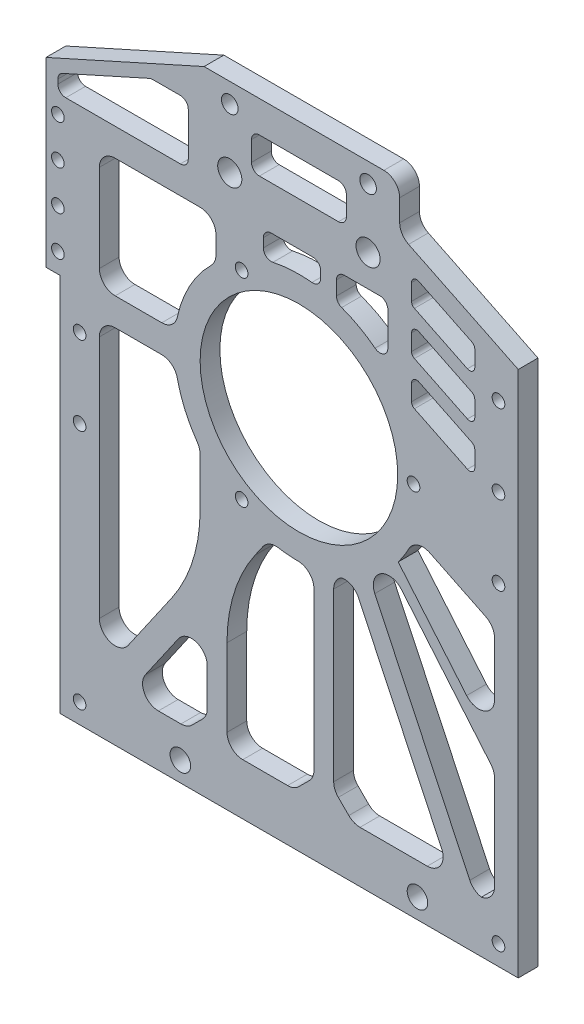
SolidWorks part; units mm, degrees
material "环氧树脂FR-4"
ref_plane "前视基准面" through (0, 0, 0) normal (0, 0, 1) x (1, 0, 0)
ref_plane "上视基准面" through (0, 0, 0) normal (0, 1, 0) x (1, 0, 0)
ref_plane "右视基准面" through (0, 0, 0) normal (1, 0, 0) x (0, 0, -1)
sketch "草图1" plane through (0, 0, 0) normal (0, 0, 1) x (1, 0, 0)
  line L1 (55.5, -80) -> (-55.5, -80)
  line L2 (55.5, -80) -> (55.5, 80)
  line L3 (55.5, 80) -> (-55.5, 80)
  line L4 (-55.5, -80) -> (-55.5, 80)
  line L5 (55.5, -80) -> (-55.5, 80) construction
  line L6 (55.5, 80) -> (-55.5, -80) construction
  point P0 (0, 0)
  dimension "D1" = 111
  dimension "D2" = 160
extrude "凸台-拉伸1" add sketch "草图1" along normal blind 5
sketch "草图2" plane through (0, 0, 5) normal (0, 0, 1) x (1, 0, 0)
  line L0 (0, 80) -> (0, -80) construction
  line L1 (55.5, 80) -> (-55.5, 80) construction
  line L2 (-55.5, -80) -> (55.5, -80) construction
  circle A0 centre (-30, -75) radius 2.6
  circle A1 centre (30, -75) radius 2.6
  dimension "D3" = 5.2
  dimension "D1" = 60
  dimension "D2" = 5
extrude "切除-拉伸1" cut sketch "草图2" against normal through all
sketch "草图3" plane through (0, 0, 5) normal (0, 0, 1) x (1, 0, 0)
  line L0 (0, 0) -> (0, 15) construction
  line L1 (-55.5, -80) -> (55.5, -80) construction
  circle A0 centre (0, 15) radius 25
  dimension "D1" = 50
  dimension "D2" = 95
extrude "切除-拉伸2" cut sketch "草图3" against normal through all
sketch "草图4" plane through (0, 0, 5) normal (0, 0, 1) x (1, 0, 0)
  line L0 (0, 15) -> (-14.5, 40.1147) construction
  line L1 (0, 15) -> (0, 40) construction
  circle A0 centre (-14.5, 40.1147) radius 1.6
  circle A1 centre (29, 15) radius 1.6
  circle A2 centre (-14.5, -10.1147) radius 1.6
  circle A3 centre (0, 15) radius 25 construction
  point P2 (0, 15)
  dimension "D3" = 3.2
  dimension "D2" = 29
  dimension "D4" = 30
  dimension "D1" = 3
extrude "切除-拉伸3" cut sketch "草图4" against normal through all
sketch "草图5" plane through (0, 0, 5) normal (0, 0, 1) x (1, 0, 0)
  point P0 (0, 15)
sketch "草图6" plane through (0, 0, 5) normal (0, 0, 1) x (1, 0, 0)
  line L0 (0, 80) -> (0, -80) construction
  line L1 (55.5, 80) -> (-55.5, 80) construction
  line L2 (-55.5, -80) -> (55.5, -80) construction
  line L4 (17.5, 60) -> (-17.5, 60) construction
  line L5 (17.5, 60) -> (17.5, 75) construction
  line L6 (17.5, 75) -> (-17.5, 75) construction
  line L7 (-17.5, 60) -> (-17.5, 75) construction
  line L8 (17.5, 60) -> (-17.5, 75) construction
  line L9 (17.5, 75) -> (-17.5, 60) construction
  circle A2 centre (-17.5, 75) radius 2.1
  circle A3 centre (17.5, 75) radius 2.1
  circle A4 centre (17.5, 60) radius 3.0525
  circle A5 centre (-17.5, 60) radius 3.0525
  point P6 (0, 67.5)
  dimension "D4" = 4.2
  dimension "D5" = 6.105
  dimension "D1" = 35
  dimension "D2" = 15
  dimension "D3" = 12.5
extrude "切除-拉伸4" cut sketch "草图6" against normal through all
sketch "草图7" plane through (0, 0, 5) normal (0, 0, 1) x (1, 0, 0)
  line L0 (-17.5, 75) -> (-17.5, 60) construction
  line L2 (17.5, 75) -> (17.5, 60) construction
  line L4 (-17.5, 67.5) -> (17.5, 67.5) construction
  line L6 (10, 63) -> (-10, 63)
  line L7 (12, 65) -> (12, 70)
  line L8 (10, 72) -> (-10, 72)
  line L9 (-12, 65) -> (-12, 70)
  line L10 (12, 63) -> (-12, 72) construction
  line L11 (12, 72) -> (-12, 63) construction
  arc A0 (12, 70) -> (10, 72) centre (10, 70) ccw
  arc A1 (10, 63) -> (12, 65) centre (10, 65) ccw
  arc A2 (-10, 63) -> (-12, 65) centre (-10, 65) cw
  arc A3 (-10, 72) -> (-12, 70) centre (-10, 70) ccw
  point P10 (0, 67.5)
  dimension "D3" = 2
  dimension "D1" = 24
  dimension "D2" = 9
extrude "切除-拉伸5" cut sketch "草图7" against normal through all
sketch "草图8" plane through (0, 0, 5) normal (0, 0, 1) x (1, 0, 0)
  line L5 (25.5, 80) -> (25.5, 68)
  line L8 (55.5, 80) -> (-55.5, 80) construction
  line L9 (25.5, 68) -> (55.5, 53.368)
  line L10 (55.5, -80) -> (55.5, 80) construction
  line L11 (55.5, 53.368) -> (55.5, 80)
  line L12 (55.5, 80) -> (25.5, 80)
  dimension "D1" = 26
  dimension "D2" = 12
  dimension "D3" = 30
extrude "切除-拉伸6" cut sketch "草图8" against normal through all
fillet "圆角1" radius 4 2 edges at (25.5, 80, 2.5) (25.5, 68, 2.5)
sketch "草图10" plane through (0, 0, 0) normal (0, 0, 1) x (1, 0, 0)
  line L0 (-55.5, 80) -> (-64, 80)
  line L1 (-64, 80) -> (-64, 16)
  line L2 (-64, 16) -> (-55.5, 16)
  line L3 (-55.5, 80) -> (-55.5, -80) construction
  line L4 (-55.5, 16) -> (-55.5, 80)
  dimension "D1" = 8.5
  dimension "D2" = 64
extrude "凸台-拉伸3" add sketch "草图10" along normal up to surface (5 mm away) up to face at (12.5699, 33.4098, 5)
sketch "草图11" plane through (0, 0, 5) normal (0, 0, 1) x (1, 0, 0)
  line L0 (-61, 41) -> (-61, 21) construction
  line L1 (-64, 80) -> (-64, 16) construction
  line L2 (-64, 16) -> (-55.5, 16) construction
  line L3 (-61, 51) -> (-61, 41) construction
  circle A0 centre (-61, 21) radius 1.6
  circle A1 centre (-61, 41) radius 1.6
  circle A2 centre (-61, 31) radius 1.6
  circle A3 centre (-61, 51) radius 1.6
  dimension "D3" = 3.2
  dimension "D1" = 20
  dimension "D2" = 3
  dimension "D4" = 5
  dimension "D5" = 10
extrude "切除-拉伸7" cut sketch "草图11" against normal through all
sketch "草图12" plane through (0, 0, 5) normal (0, 0, 1) x (1, 0, 0)
  line L0 (-64, 80) -> (-64, 62)
  line L1 (-64, 80) -> (-64, 16) construction
  line L2 (-64, 62) -> (-24, 80)
  line L3 (21.5, 80) -> (-64, 80) construction
  line L4 (-24, 80) -> (-64, 80)
  dimension "D1" = 18
  dimension "D2" = 40
extrude "切除-拉伸8" cut sketch "草图12" against normal through all
sketch "草图13" plane through (0, 0, 0) normal (0, 0, 1) x (1, 0, 0)
  line L0 (-55.5, -80) -> (-60.5, -80)
  line L1 (-60.5, -80) -> (-60.5, 16)
  line L2 (-64, 16) -> (-55.5, 16) construction
  line L3 (-60.5, 16) -> (-55.5, 16)
  line L4 (-55.5, 16) -> (-55.5, -80) construction
  line L5 (-55.5, 16) -> (-55.5, -80)
  dimension "D1" = 5
extrude "凸台-拉伸4" add sketch "草图13" along normal up to surface (5 mm away) up to face at (-4.6764, 32.8435, 5)
sketch "草图19" plane through (0, 0, 5) normal (0, 0, 1) x (1, 0, 0)
  line L0 (-55.5, -75) -> (50.5, -75) construction
  line L1 (-60.5, 16) -> (-60.5, -80) construction
  line L2 (-60.5, -80) -> (55.5, -80) construction
  line L3 (-55.5, 6) -> (-55.5, -14) construction
  line L4 (-64, 16) -> (-60.5, 16) construction
  line L5 (50.5, 44) -> (50.5, 24) construction
  line L6 (55.5, -80) -> (55.5, 53.368) construction
  line L7 (50.5, 24) -> (50.5, 4) construction
  circle A0 centre (-55.5, -75) radius 1.6
  circle A1 centre (50.5, -75) radius 1.6
  circle A2 centre (-55.5, 6) radius 1.6
  circle A3 centre (-55.5, -14) radius 1.6
  circle A4 centre (50.5, 44) radius 1.6
  circle A5 centre (50.5, 24) radius 1.6
  circle A6 centre (50.5, 4) radius 1.6
  dimension "D1" = 3.2
  dimension "D2" = 5
  dimension "D11" = 20
  dimension "D3" = 5
  dimension "D4" = 20
  dimension "D5" = 5
  dimension "D6" = 10
  dimension "D7" = 5
  dimension "D8" = 20
  dimension "D9" = 5
  dimension "D10" = 44
extrude "切除-拉伸13" cut sketch "草图19" against normal through all
sketch "草图14" plane through (0, 0, 5) normal (0, 0, 1) x (1, 0, 0)
  line L0 (28.5, 60.9738) -> (44.5, 53.1701)
  line L1 (44.5, 53.1701) -> (44.5, 46.1701)
  line L2 (44.5, 46.1701) -> (28.5, 53.9738)
  line L3 (28.5, 53.9738) -> (28.5, 60.9738)
  line L4 (27.7465, 66.9043) -> (55.5, 53.368) construction
  line L5 (55.5, -80) -> (55.5, 53.368) construction
  line L6 (25.5, 76) -> (25.5, 70.4995) construction
  dimension "D1" = 5
  dimension "D2" = 11
  dimension "D3" = 3
  dimension "D4" = 7
extrude "切除-拉伸9" cut sketch "草图14" against normal through all
fillet "圆角2" radius 1.3 4 edges at (44.5, 46.1701, 2.5) (44.5, 53.1701, 2.5) (28.5, 53.9738, 2.5) (28.5, 60.9738, 2.5)
pattern_linear "阵列(线性)1" count 3 spacing 11 along (0, -1, 0) of "切除-拉伸9", "圆角2"
sketch "草图17" plane through (0, 0, 5) normal (0, 0, 1) x (1, 0, 0)
  line L0 (-61, 60.0602) -> (-37.4444, 70.6602)
  line L1 (-28, 70.6602) -> (-28, 55.6602)
  line L3 (-64, 62) -> (-24, 80) construction
  line L4 (-61, 60.0602) -> (-61, 55.6602)
  line L5 (-61, 55.6602) -> (-28, 55.6602)
  line L6 (-64, 62) -> (-64, 16) construction
  line L7 (-37.4444, 70.6602) -> (-28, 70.6602)
  dimension "D1" = 3
  dimension "D2" = 3
  dimension "D3" = 4.4
  dimension "D4" = 33
  dimension "D5" = 15
extrude "切除-拉伸11" cut sketch "草图17" against normal through all
sketch "草图16" plane through (0, 0, 5) normal (0, 0, 1) x (1, 0, 0)
  line L0 (-27, 70.9739) -> (-53, 59.2739)
  line L1 (-53, 59.2739) -> (-53, 48.2739)
  line L2 (-53, 48.2739) -> (-27, 59.9739)
  line L3 (-27, 59.9739) -> (-27, 70.9739)
  line L5 (-22.8002, 51.1888) -> (-22.8002, 20.9929)
  line L8 (-64, 62) -> (-24, 80) construction
  line L13 (-64, 62) -> (-64, 16) construction
  line L21 (-51.6219, 38.219) -> (-51.6219, 20.984)
  line L22 (-51.6219, 38.219) -> (-22.8002, 51.1888)
  line L23 (-22.8002, 20.9929) -> (-51.6219, 20.984)
  circle A0 centre (0, 15) radius 29
  circle A1 centre (0, 15) radius 34
  dimension "D1" = 68
  dimension "D2" = 7
  dimension "D3" = 11
  dimension "D4" = 11
  dimension "D5" = 3
  dimension "D6" = 6
fillet "圆角3" radius 2 5 edges at (-61, 60.0602, 2.5) (-28, 55.6602, 2.5) (-28, 70.6602, 2.5) (-37.4444, 70.6602, 2.5) (-61, 55.6602, 2.5)
sketch "草图18" plane through (0, 0, 5) normal (0, 0, 1) x (1, 0, 0)
  line L0 (-50.5, 48.6602) -> (-21, 48.6602)
  line L1 (-21, 48.6602) -> (-21, 38.4787)
  line L2 (-50.5, 48.6602) -> (-50.5, 18.5)
  line L3 (-50.5, 18.5) -> (-31.305, 18.5)
  line L4 (-60.5, 16) -> (-60.5, -80) construction
  line L5 (8.7974, -15.2466) -> (8.7974, -67)
  line L6 (8.7974, -67) -> (38.7974, -67)
  line L7 (-31.305, 11.5) -> (-50.5, 11.5)
  line L8 (-50.5, 11.5) -> (-50.5, -67)
  line L9 (-50.5, -67) -> (-25, -30.1638)
  line L10 (-25, -30.1638) -> (-25, -4.1638)
  line L11 (-43.2026, -67) -> (-23.2026, -38.1088)
  line L12 (-43.2026, -67) -> (-23.2026, -67)
  line L13 (3.7974, -67) -> (3.7974, -16.2703)
  line L14 (38.7974, -67) -> (13.472, -13.4737)
  line L15 (29.4362, 3.7858) -> (49.5, -6)
  line L16 (49.5, -6) -> (49.5, -67)
  line L17 (44.3288, -67) -> (17.8209, -10.9743)
  line L18 (-23.2026, -38.1088) -> (-23.2026, -67)
  line L19 (-18.2026, -30.886) -> (-18.2026, -67)
  line L20 (-18.2026, -67) -> (3.7974, -67)
  line L21 (-18.2026, -30.886) -> (-7.5997, -15.5695)
  line L22 (-59, 55.6602) -> (-30, 55.6602) construction
  line L23 (-60.5, -80) -> (55.5, -80) construction
  line L24 (44.3288, -67) -> (49.5, -67)
  line L25 (55.5, -80) -> (55.5, 53.368) construction
  line L26 (27.7465, 66.9043) -> (55.5, 53.368) construction
  line L27 (25.1247, -4) -> (49.5, -33.0494)
  line L28 (49.5, -37.7165) -> (23.1711, -6.339)
  circle A0 centre (0, 15) radius 31.5
  circle A1 centre (50.5, 4) radius 1.6 construction
  dimension "D1" = 63
  dimension "D2" = 10
  dimension "D3" = 3.5
  dimension "D4" = 7
  dimension "D5" = 21
  dimension "D6" = 3.5
  dimension "D7" = 25
  dimension "D8" = 13
  dimension "D9" = 6
  dimension "D10" = 13
  dimension "D11" = 20
  dimension "D12" = 5
  dimension "D13" = 26
  dimension "D14" = 22
  dimension "D15" = 5
  dimension "D16" = 13
  dimension "D17" = 30
  dimension "D18" = 5
  dimension "D19" = 6
  dimension "D20" = 10
  dimension "D21" = 40
  dimension "D22" = 3
  dimension "D23" = 19
extrude "切除-拉伸12" cut sketch "草图18" against normal blind 10 contours A0 L1 L0 L2 L3 | A0 L7 L8 L9 L10 | A0 L11 L12 L13 | A0 L5 L6 L14 | A0 L21 L19 L20 L13 | A0 L17 L24 L16 L28 | A0 L27 L16 L15 | L11 L18 L12 region at (-37.6585, 34.9225, 5) region at (-39.5472, -20.5511, 5) region at (39.8826, -11.5595, 5) region at (-6.6688, -43.084, 5) region at (36.9414, -36.5854, 5) region at (19.0491, -46.9108, 5) region at (-29.8693, -57.3696, 5)
fillet "圆角5" radius 40 2 edges at (-25, -30.1638, 2.5) (-18.2026, -30.886, 2.5)
chamfer "倒角1" distance 5 angle 45 3 edges at (-23.2026, -67, 2.5) (8.7974, -67, 2.5) (3.7974, -67, 2.5)
fillet "圆角6" radius 4 31 edges at (-31.305, 18.5, 2.5) (-50.5, 18.5, 2.5) (-50.5, 48.6602, 2.5) (-21, 48.6602, 2.5) (-21, 38.4787, 2.5) (38.7974, -67, 2.5) (13.7974, -67, 2.5) (8.7974, -62, 2.5) (8.7974, -15.2466, 2.5) (-25, -4.1638, 2.5) (-50.5, -67, 2.5) (-50.5, 11.5, 2.5) (-31.305, 11.5, 2.5) (-23.2026, -38.1088, 2.5) (-23.2026, -62, 2.5) (-28.2026, -67, 2.5) (-43.2026, -67, 2.5) (49.5, -67, 2.5) (44.3288, -67, 2.5) (17.8209, -10.9743, 2.5) (3.7974, -62, 2.5) (-1.2026, -67, 2.5) (-18.2026, -67, 2.5) (49.5, -6, 2.5) (29.4362, 3.7858, 2.5) (13.472, -13.4737, 2.5) (3.7974, -16.2703, 2.5) (-7.5997, -15.5695, 2.5) (49.5, -37.7165, 2.5) (49.5, -33.0494, 2.5) (23.1711, -6.339, 2.5)
sketch "草图20" plane through (0, 0, 5) normal (0, 0, 1) x (1, 0, 0)
  line L0 (-9, 45.1869) -> (-9, 52)
  line L1 (-9, 52) -> (22.5, 52)
  line L2 (22.5, 52) -> (22.5, 37.0454)
  line L3 (-21, 44.6602) -> (-21, 40.2042) construction
  line L4 (28.5, 47.8934) -> (28.5, 43.7861) construction
  line L5 (5.5, 52) -> (5.5, 46.0161)
  line L6 (9.5, 52) -> (9.5, 45.0333)
  arc A0 (22.5, 37.0454) -> (-9, 45.1869) centre (0, 15) ccw
  circle A1 centre (17.5, 60) radius 3.0525 construction
  dimension "D1" = 63
  dimension "D2" = 12
  dimension "D3" = 8
  dimension "D4" = 6
  dimension "D5" = 13
  dimension "4" = 4
extrude "切除-拉伸14" cut sketch "草图20" against normal through all contours A0 L5 L1 L0 | A0 L2 L1 L6 region at (-1.92, 49.0745, 5) region at (16.8322, 46.6311, 5)
fillet "圆角7" radius 2 8 edges at (22.5, 52, 2.5) (22.5, 37.0454, 2.5) (-9, 45.1869, 2.5) (-9, 52, 2.5) (9.5, 45.0333, 2.5) (9.5, 52, 2.5) (5.5, 46.0161, 2.5) (5.5, 52, 2.5)
